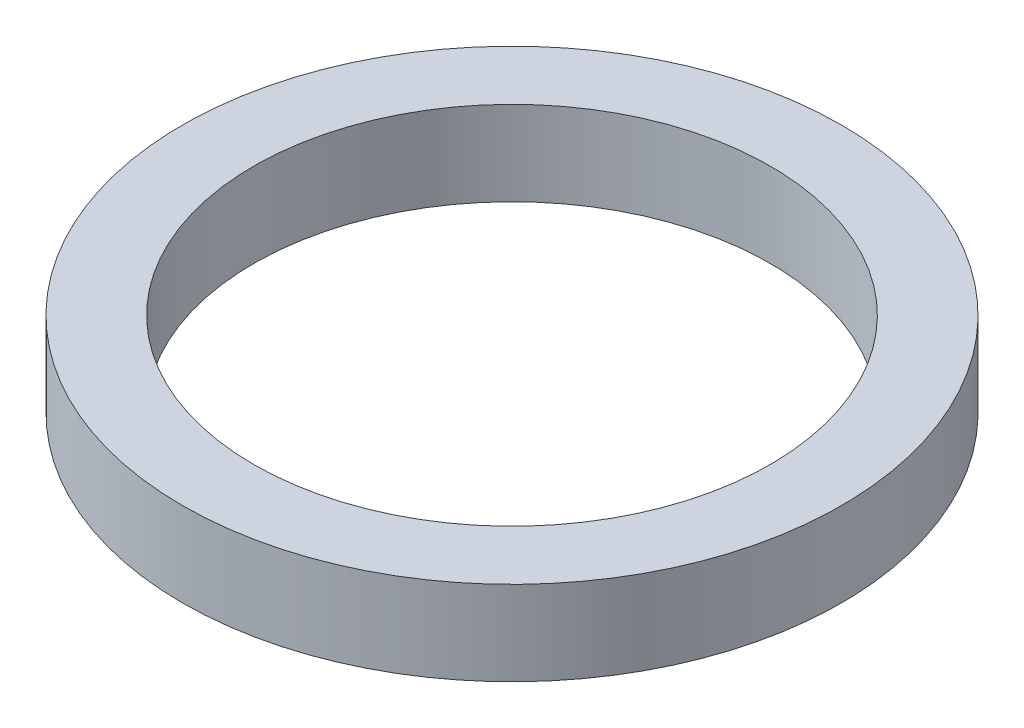
SolidWorks part; units mm, degrees
ref_plane "Front Plane" through (0, 0, 0) normal (0, 0, 1) x (1, 0, 0)
ref_plane "Top Plane" through (0, 0, 0) normal (0, 1, 0) x (1, 0, 0)
ref_plane "Right Plane" through (0, 0, 0) normal (1, 0, 0) x (0, 0, -1)
sketch "Sketch1" plane through (0, 0, 0) normal (0, 1, 0) x (1, 0, 0)
  circle A0 centre (0, 0) radius 17.15
  circle A1 centre (0, 0) radius 21.875
  dimension "D1" = 34.3
  dimension "D2" = 43.75
extrude "Boss-Extrude1" add sketch "Sketch1" along normal blind 5.6
